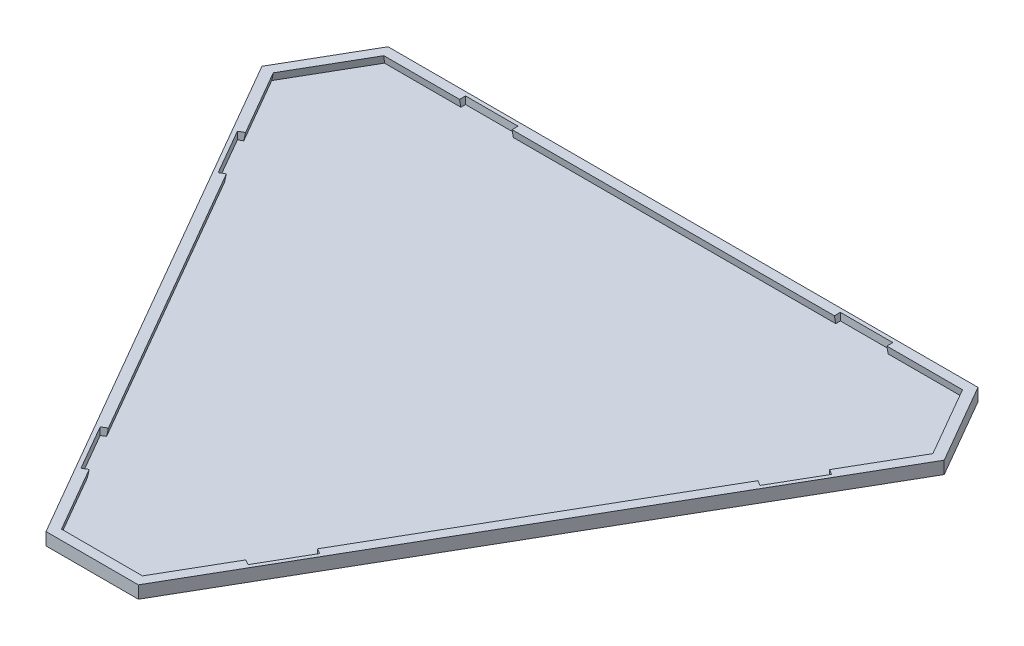
SolidWorks part; units mm, degrees
ref_plane "Plan de face" through (0, 0, 0) normal (0, 0, 1) x (1, 0, 0)
ref_plane "Plan de dessus" through (0, 0, 0) normal (0, 1, 0) x (1, 0, 0)
ref_plane "Plan de droite" through (0, 0, 0) normal (1, 0, 0) x (0, 0, -1)
sketch "Esquisse2" plane through (0, 0, 0) normal (0, 1, 0) x (1, 0, 0)
  line L3 (-59.0248, 44.7446) -> (-68.2624, 28.7446) construction
  line L4 (-59.0248, 44.7446) -> (59.0248, 44.7446) construction
  line L5 (68.2624, 28.7446) -> (9.2376, -73.4893) construction
  line L6 (-68.2624, 28.7446) -> (-59.0248, 44.7446)
  line L7 (59.0248, 44.7446) -> (68.2624, 28.7446)
  line L8 (9.2376, -73.4893) -> (-9.2376, -73.4893)
  line L9 (-68.2624, 28.7446) -> (-9.2376, -73.4893)
  line L10 (9.2376, -73.4893) -> (68.2624, 28.7446)
  line L11 (59.0248, 44.7446) -> (-59.0248, 44.7446)
  line L12 (-9.2376, -73.4893) -> (-68.2624, 28.7446) construction
  line L13 (-9.2376, -73.4893) -> (9.2376, -73.4893) construction
  line L14 (68.2624, 28.7446) -> (59.0248, 44.7446) construction
  point P16 (0, 0)
extrude "Boss.-Extru.2" add sketch "Esquisse2" along normal blind 1
sketch "Esquisse5" plane through (0, 1, 0) normal (0, 1, 0) x (1, 0, 0)
  line L19 (-68.2624, 28.7446) -> (-9.2376, -73.4893)
  line L20 (-9.2376, -73.4893) -> (9.2376, -73.4893)
  line L21 (9.2376, -73.4893) -> (68.2624, 28.7446)
  line L26 (68.2624, 28.7446) -> (59.0248, 44.7446)
  line L27 (59.0248, 44.7446) -> (-59.0248, 44.7446)
  line L32 (-59.0248, 44.7446) -> (-68.2624, 28.7446)
  line L37 (-68.2624, 28.7446) -> (-9.2376, -73.4893)
  line L38 (-9.2376, -73.4893) -> (9.2376, -73.4893)
  line L39 (9.2376, -73.4893) -> (68.2624, 28.7446)
  line L44 (68.2624, 28.7446) -> (59.0248, 44.7446)
  line L45 (59.0248, 44.7446) -> (-59.0248, 44.7446)
  line L50 (-59.0248, 44.7446) -> (-68.2624, 28.7446)
  dimension "D1" = 0
extrude "Extru.-Mince1" add sketch "Esquisse5" along normal blind 1.5 draft 10 thin draft outward yes thin type one direction reverse wall 1.7
sketch "Esquisse6" plane through (0, 0, 0) normal (0, -1, 0) x (1, 0, 0)
  line L6 (-59.0248, -44.7446) -> (59.0248, -44.7446)
  line L7 (59.0248, -44.7446) -> (68.2624, -28.7446)
  line L8 (68.2624, -28.7446) -> (9.2376, 73.4893)
  line L9 (9.2376, 73.4893) -> (-9.2376, 73.4893)
  line L10 (-9.2376, 73.4893) -> (-68.2624, -28.7446)
  line L11 (-68.2624, -28.7446) -> (-59.0248, -44.7446)
  line L12 (-59.0248, -44.7446) -> (59.0248, -44.7446)
  line L13 (59.0248, -44.7446) -> (68.2624, -28.7446)
  line L14 (68.2624, -28.7446) -> (9.2376, 73.4893)
  line L15 (9.2376, 73.4893) -> (-9.2376, 73.4893)
  line L16 (-9.2376, 73.4893) -> (-68.2624, -28.7446)
  line L17 (-68.2624, -28.7446) -> (-59.0248, -44.7446)
  dimension "D1" = 0
extrude "Enlèv. de mat.-Extru.-Mince1" cut sketch "Esquisse6" against normal through all thin thin type one direction wall 1.5
sketch "Esquisse7" plane through (0, 1, 0) normal (0, 1, 0) x (1, 0, 0)
  line L0 (2.25, 44.7446) -> (-2.25, 44.7446)
  line L1 (2.25, 44.7446) -> (2.25, 40.6446)
  line L2 (-2.25, 44.7446) -> (-2.25, 40.6446)
  line L3 (2.25, 40.6446) -> (-2.25, 40.6446)
  line L4 (-59.0248, 44.7446) -> (59.0248, 44.7446) construction
  line L5 (34.0743, -22.2709) -> (36.3243, -18.3738)
  line L6 (37.625, -24.3209) -> (34.0743, -22.2709)
  line L7 (37.625, -24.3209) -> (39.875, -20.4238)
  line L8 (39.875, -20.4238) -> (36.3243, -18.3738)
  line L9 (-36.3243, -18.3738) -> (-34.0743, -22.2709)
  line L10 (-39.875, -20.4238) -> (-36.3243, -18.3738)
  line L11 (-39.875, -20.4238) -> (-37.625, -24.3209)
  line L12 (-37.625, -24.3209) -> (-34.0743, -22.2709)
  point P6 (0, 44.7446)
  point P7 (0, 44.7446)
  point P19 (0, 0)
  dimension "D1" = 4.1
  dimension "D2" = 4.5
  dimension "D3" = 3
extrude "Boss.-Extru.5" [suppressed] add sketch "Esquisse7" along normal up to surface (1.5 mm away) up to face at (0, 2.5, 0)
sketch "Esquisse8" [suppressed] plane through (0, 1, 0) normal (0, 1, 0) x (1, 0, 0)
  line L0 (-2.25, 40.6446) -> (2.25, 40.6446) construction
  line L1 (-5, 40.6446) -> (5, 40.6446)
  line L2 (-5, 40.6446) -> (-5, 38.6446)
  line L3 (-5, 38.6446) -> (5, 38.6446)
  line L4 (5, 40.6446) -> (5, 38.6446)
  line L5 (37.6993, -15.9922) -> (32.6993, -24.6524)
  line L6 (37.6993, -15.9922) -> (35.9672, -14.9922)
  line L7 (35.9672, -14.9922) -> (30.9672, -23.6524)
  line L8 (32.6993, -24.6524) -> (30.9672, -23.6524)
  line L9 (-32.6993, -24.6524) -> (-37.6993, -15.9922)
  line L10 (-32.6993, -24.6524) -> (-30.9672, -23.6524)
  line L11 (-30.9672, -23.6524) -> (-35.9672, -14.9922)
  line L12 (-37.6993, -15.9922) -> (-35.9672, -14.9922)
  point P7 (0, 40.6446)
  point P8 (0, 40.6446)
  point P18 (0, 0)
  dimension "D1" = 10
  dimension "D2" = 2
  dimension "D3" = 3
extrude "Boss.-Extru.6" [suppressed] add sketch "Esquisse8" along normal blind 2.2
sketch "Esquisse9" [suppressed] plane through (0, 3.2, 0) normal (0, 1, 0) x (1, 0, 0)
  line L1 (0.6, 40.9446) -> (-0.6, 40.9446)
  line L2 (0.6, 40.9446) -> (0.6, 38.6446)
  line L3 (0.6, 38.6446) -> (-0.6, 38.6446)
  line L4 (-0.6, 40.9446) -> (-0.6, 38.6446)
  line L6 (35.1591, -20.9919) -> (35.7591, -19.9527)
  line L7 (35.1591, -20.9919) -> (33.1672, -19.8419)
  line L8 (33.1672, -19.8419) -> (33.7672, -18.8027)
  line L9 (35.7591, -19.9527) -> (33.7672, -18.8027)
  line L10 (-35.7591, -19.9527) -> (-35.1591, -20.9919)
  line L11 (-35.7591, -19.9527) -> (-33.7672, -18.8027)
  line L12 (-33.7672, -18.8027) -> (-33.1672, -19.8419)
  line L13 (-35.1591, -20.9919) -> (-33.1672, -19.8419)
  line L14 (-2.25, 40.6446) -> (2.25, 40.6446) construction
  line L15 (5, 40.6446) -> (-5, 40.6446) construction
  line L16 (-5, 38.6446) -> (5, 38.6446) construction
  point P4 (0, 40.9446)
  point P7 (0, 0)
  point P9 (0, 40.6446)
  point P21 (0, 0)
  dimension "D1" = 1.2
  dimension "D2" = 3
  dimension "D3" = 0.3
extrude "Boss.-Extru.7" [suppressed] add sketch "Esquisse9" along normal blind 3 and the other way up to next
sketch "Esquisse10" plane through (0, 2.5, 0) normal (0, 1, 0) x (1, 0, 0)
  line L0 (0, 44.7446) -> (0, 32.7785) construction
  line L1 (-32.25, 43.9802) -> (-42.75, 43.9802)
  line L2 (-32.25, 43.9802) -> (-32.25, 39.7025)
  line L3 (-32.25, 39.7025) -> (-42.75, 39.7025)
  line L4 (-42.75, 43.9802) -> (-42.75, 39.7025)
  line L5 (57.8906, 42.7802) -> (-57.8906, 42.7802) construction
  line L7 (-59.0248, 44.7446) -> (59.0248, 44.7446) construction
  line L8 (42.75, 43.9802) -> (42.75, 39.7025)
  line L9 (32.25, 39.7025) -> (42.75, 39.7025)
  line L10 (32.25, 43.9802) -> (32.25, 39.7025)
  line L11 (32.25, 43.9802) -> (42.75, 43.9802)
  line L12 (54.2129, 5.9392) -> (59.4629, 15.0325)
  line L13 (54.2129, 5.9392) -> (50.5084, 8.0781)
  line L14 (50.5084, 8.0781) -> (55.7584, 17.1713)
  line L15 (59.4629, 15.0325) -> (55.7584, 17.1713)
  line L16 (16.7129, -59.0127) -> (13.0084, -56.8738)
  line L17 (18.2584, -47.7806) -> (13.0084, -56.8738)
  line L18 (21.9629, -49.9194) -> (18.2584, -47.7806)
  line L19 (21.9629, -49.9194) -> (16.7129, -59.0127)
  line L20 (-21.9629, -49.9194) -> (-16.7129, -59.0127)
  line L21 (-21.9629, -49.9194) -> (-18.2584, -47.7806)
  line L22 (-18.2584, -47.7806) -> (-13.0084, -56.8738)
  line L23 (-16.7129, -59.0127) -> (-13.0084, -56.8738)
  line L24 (-59.4629, 15.0325) -> (-55.7584, 17.1713)
  line L25 (-50.5084, 8.0781) -> (-55.7584, 17.1713)
  line L26 (-54.2129, 5.9392) -> (-50.5084, 8.0781)
  line L27 (-54.2129, 5.9392) -> (-59.4629, 15.0325)
  point P11 (-37.5, 43.9802)
  point P35 (0, 0)
  dimension "D1" = 1.2
  dimension "D2" = 10.5
  dimension "D3" = 75
  dimension "D4" = 3
extrude "Enlèv. mat.-Extru.1" cut sketch "Esquisse10" against normal up to surface (1.5 mm away) up to face at (0, 1, 0)
